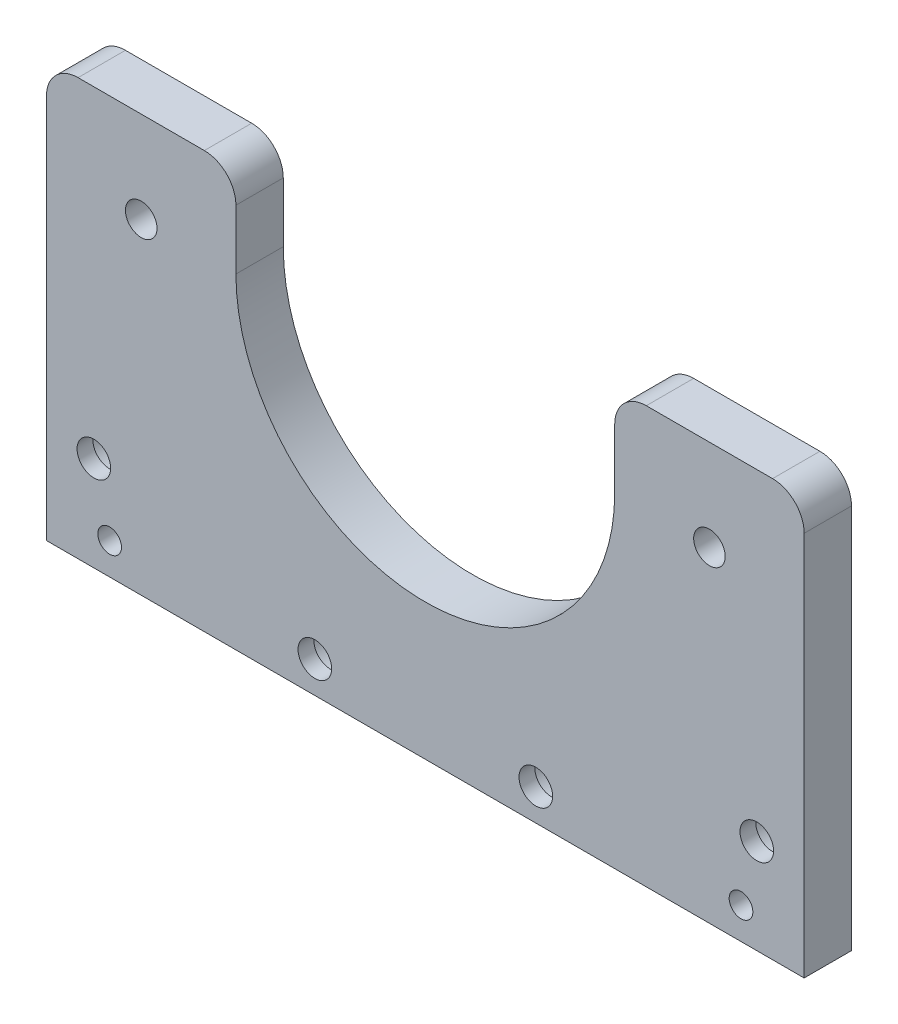
SolidWorks part; units mm, degrees
material "6061 Alloy"
ref_plane "Front" through (0, 0, 0) normal (0, 0, 1) x (1, 0, 0)
ref_plane "Top" through (0, 0, 0) normal (0, 1, 0) x (1, 0, 0)
ref_plane "Right" through (0, 0, 0) normal (1, 0, 0) x (0, 0, -1)
ref_axis "Axis" through (0, 0, -80.9) along (0, 0, 1)
sketch "Sketch1" plane through (0, 0, 0) normal (0, 0, 1) x (1, 0, 0)
  line L0 (0, -65.4837) -> (0, 0) construction
  line L1 (76.2, 11.9863) -> (76.2, -65.4837)
  line L2 (57.15, 0) -> (-57.15, 0) construction
  line L3 (38.1, 0) -> (38.1, 11.9863)
  line L4 (-38.1, 0) -> (-38.1, 11.9863)
  line L5 (69.85, 18.3363) -> (44.45, 18.3363)
  line L6 (-69.85, 18.3363) -> (-44.45, 18.3363)
  line L31 (76.2, -65.4837) -> (-76.2, -65.4837)
  line L34 (-76.2, 11.9863) -> (-76.2, -65.4837)
  arc A0 (-44.45, 18.3363) -> (-38.1, 11.9863) centre (-44.45, 11.9863) cw
  circle A1 centre (-57.15, 0) radius 3.175
  circle A2 centre (57.15, 0) radius 3.175
  arc A3 (76.2, 11.9863) -> (69.85, 18.3363) centre (69.85, 11.9863) ccw
  arc A4 (44.45, 18.3363) -> (38.1, 11.9863) centre (44.45, 11.9863) ccw
  arc A5 (-76.2, 11.9863) -> (-69.85, 18.3363) centre (-69.85, 11.9863) cw
  arc A6 (-38.1, 0) -> (38.1, 0) centre (0, 0) ccw
  dimension "D2" = 6.35
  dimension "D3" = 83.82
  dimension "D5" = 38.1
  dimension "D7" = 6.35
  dimension "D4" = 65.4837
  dimension "D6" = 152.4
  dimension "D10" = 114.3
extrude "Base" add sketch "Sketch1" along normal mid plane 9.525
hole_wizard "1/4 Cap screw carriage mounts" positions "Sketch6" profile "Sketch5" counterbore size "1/4" standard "Ansi Inch" end condition through all
sketch "Sketch6" plane through (-61.9874, 5.4091, -4.7625) normal (0, 0, 1) x (1, 0, 0)
  line L2 (84.2124, -64.5428) -> (39.7624, -64.5428) construction
  line L3 (39.7624, -64.5428) -> (-4.6876, -64.5428) construction
  line L4 (84.2124, -64.5428) -> (128.6624, -64.5428) construction
  line L5 (61.9874, -5.4091) -> (61.9874, -64.5428) construction
  line L7 (-14.2126, -70.8928) -> (138.1874, -70.8928) construction
  point P0 (-4.6876, -51.8428)
  point P1 (39.7624, -64.5428)
  point P3 (128.6624, -51.8428)
  point P5 (84.2124, -64.5428)
  dimension "D2" = 19.05
  dimension "D3" = 6.35
  dimension "D5" = 44.45
sketch "Sketch5" plane through (-66.675, -46.4337, -4.7625) normal (1, 0, 0) x (0, 1, 0)
  line L0 (0, 0) -> (0, 9.525)
  line L1 (0, 9.525) -> (3.3782, 9.525)
  line L3 (3.3782, 9.525) -> (3.3782, 6.35)
  line L4 (3.3782, 6.35) -> (5.5562, 6.35)
  line L5 (5.5562, 6.35) -> (5.5562, 0)
  line L7 (5.5562, 0) -> (0, 0)
  line L11 (0, -6.35) -> (0, 107.95) construction
  dimension "Thru Hole Dia." = 6.7564
  dimension "Thru Hole Depth" = 9.525
  dimension "C'Bore Dia." = 11.1125
  dimension "C'Bore Depth" = 6.35
sketch "Sketch8" plane through (0, 0, -4.7625) normal (0, 0, -1) x (-1, 0, 0)
  line L0 (76.2, -65.4837) -> (-76.2, -65.4837) construction
  line L1 (64.262, -65.4837) -> (39.751, -65.4837)
  line L2 (64.262, -65.4837) -> (64.262, -64.9757)
  line L3 (64.262, -64.9757) -> (39.751, -64.9757)
  line L4 (39.751, -65.4837) -> (39.751, -64.9757)
  line L5 (0, -65.4837) -> (0, 0) construction
  line L6 (76.2, 11.9863) -> (76.2, -65.4837) construction
  line L7 (-39.751, -65.4837) -> (-39.751, -64.9757)
  line L8 (-64.262, -64.9757) -> (-39.751, -64.9757)
  line L9 (-64.262, -65.4837) -> (-64.262, -64.9757)
  line L10 (-64.262, -65.4837) -> (-39.751, -65.4837)
  line L11 (-76.2, -65.4837) -> (-76.2, -64.9757)
  line L12 (73.025, -65.4837) -> (76.2, -65.4837)
  line L13 (73.025, -65.4837) -> (73.025, -64.9757)
  line L14 (73.025, -64.9757) -> (76.2, -64.9757)
  line L15 (76.2, -65.4837) -> (76.2, -64.9757)
  line L16 (-73.025, -64.9757) -> (-76.2, -64.9757)
  line L17 (-73.025, -65.4837) -> (-73.025, -64.9757)
  line L18 (-73.025, -65.4837) -> (-76.2, -65.4837)
  dimension "D1" = 11.938
  dimension "D2" = 36.449
  dimension "D3" = 0.508
  dimension "D4" = 3.175
extrude "Misc. cut" [suppressed] cut sketch "Sketch8" against normal through all
fillet "Top edge safety fillet" [suppressed] radius 1.5875
sketch "Sketch9" plane through (0, 0, 4.7625) normal (0, 0, -1) x (-1, 0, 0)
  line L0 (0, 0) -> (0, -104.4847) construction
  line L1 (-62.7062, -59.1337) -> (-64.2937, -59.1337) construction
  line L2 (-62.7062, -61.515) -> (-64.2937, -61.515) construction
  line L3 (-62.7062, -56.7525) -> (-64.2937, -56.7525) construction
  circle A0 centre (63.5, -59.1337) radius 2.3813
  circle A1 centre (-63.5, -59.1337) radius 2.3812
  arc A2 (-62.7062, -61.515) -> (-62.7062, -56.7525) centre (-62.7062, -59.1337) ccw construction
  arc A3 (-64.2937, -56.7525) -> (-64.2937, -61.515) centre (-64.2937, -59.1337) ccw construction
  point P9 (-63.5, -59.1337)
  dimension "D1" = 4.7625
  dimension "D2" = 127
  dimension "D3" = 1.5875
extrude "Alignment_pin_holes" cut sketch "Sketch9" along normal blind 6.35
